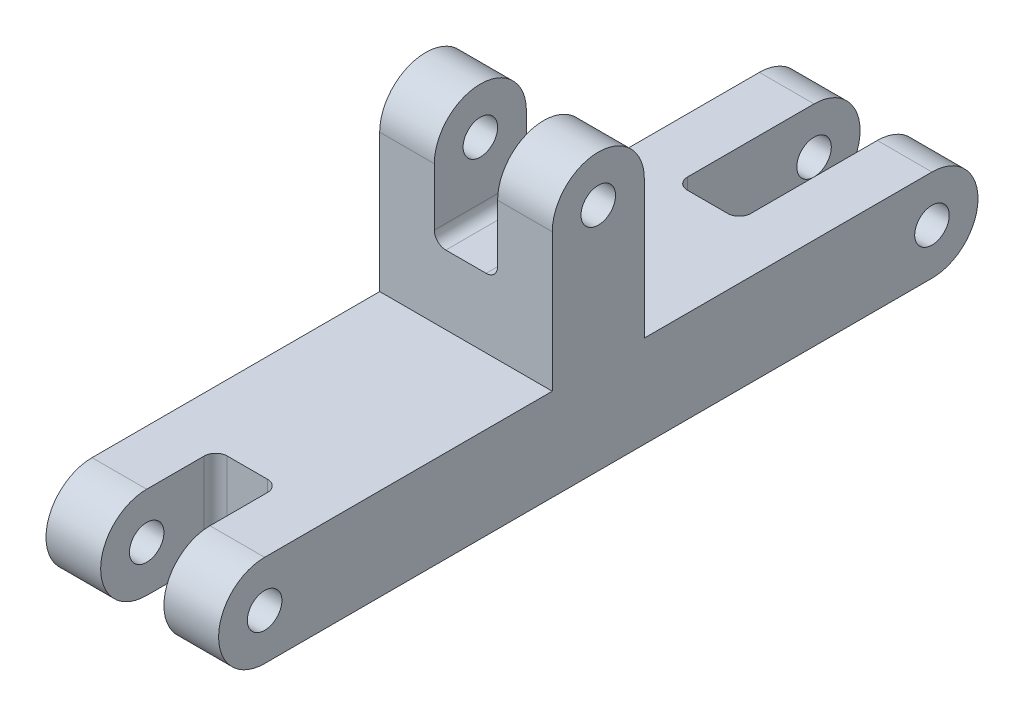
SolidWorks part; units mm, degrees
ref_plane "Alzado" through (0, 0, 0) normal (0, 0, 1) x (1, 0, 0)
ref_plane "Planta" through (0, 0, 0) normal (0, 1, 0) x (1, 0, 0)
ref_plane "Vista lateral" through (0, 0, 0) normal (1, 0, 0) x (0, 0, -1)
sketch "Croquis1" plane through (0, 0, 0) normal (1, 0, 0) x (0, 0, -1)
  line L0 (-15, 0) -> (15, 0) construction
  line L1 (-15, 4) -> (-18, 4) construction
  line L2 (-15, -4) -> (15, -4)
  line L3 (-10, 4) -> (15, 4)
  line L5 (-18, 4) -> (-18, 16)
  line L6 (-18, 16) -> (-10, 16) construction
  line L7 (-10, 4) -> (-10, 16)
  line L8 (-18, 4) -> (-43, 4)
  line L9 (-15, -4) -> (-43, -4)
  line L10 (-43, 4) -> (-43, -4) construction
  arc A0 (-15, 4) -> (-15, -4) centre (-15, 0) ccw construction
  arc A1 (15, -4) -> (15, 4) centre (15, 0) ccw
  circle A2 centre (15, 0) radius 1.5
  arc A3 (-10, 16) -> (-18, 16) centre (-14, 16) ccw
  circle A4 centre (-14, 16) radius 1.5
  circle A5 centre (-15, 0) radius 1.5 construction
  arc A6 (-43, 4) -> (-43, -4) centre (-43, 0) ccw
  circle A7 centre (-43, 0) radius 1.5
  point P3 (0, 0)
  dimension "D2" = 4
  dimension "D3" = 3
  dimension "D4" = 4
  dimension "D7" = 25
  dimension "D1" = 30
  dimension "D5" = 25
  dimension "D6" = 12
extrude "Saliente-Extruir1" add sketch "Croquis1" along normal mid plane 15
sketch "Croquis2" plane through (0, 0, 0) normal (1, 0, 0) x (0, 0, -1)
  line L0 (-18, 16) -> (-18, 4) construction
  line L1 (-18, 10) -> (-10, 10)
  line L2 (-18, 10) -> (-18, 20)
  line L3 (-18, 20) -> (-10, 20)
  line L4 (-10, 10) -> (-10, 20)
  line L5 (-10, 4) -> (-10, 16) construction
  line L11 (-43, -4) -> (15, -4) construction
  line L12 (15, 4) -> (-10, 4) construction
  line L13 (3, 4) -> (19, 4)
  line L14 (3, 4) -> (3, -4)
  line L15 (3, -4) -> (19, -4)
  line L16 (19, 4) -> (19, -4)
  line L18 (-37, 4) -> (-47, 4)
  line L19 (-37, 4) -> (-37, -4)
  line L20 (-37, -4) -> (-47, -4)
  line L21 (-47, 4) -> (-47, -4)
  line L22 (-43, -4) -> (15, -4) construction
  line L23 (-18, 4) -> (-43, 4) construction
  arc A0 (-10, 16) -> (-18, 16) centre (-14, 16) ccw construction
  arc A2 (15, -4) -> (15, 4) centre (15, 0) ccw construction
  arc A5 (-43, 4) -> (-43, -4) centre (-43, 0) ccw construction
  dimension "D5" = 10
  dimension "D1" = 10
  dimension "D3" = 16
extrude "Cortar-Extruir1" cut sketch "Croquis2" against normal mid plane 5.5
fillet "Redondeo1" radius 1 6 edges at (2.75, 0, 37) (-2.75, 0, 37) (2.75, 0, -3) (-2.75, 0, -3) (2.75, 10, 14) (-2.75, 10, 14)
